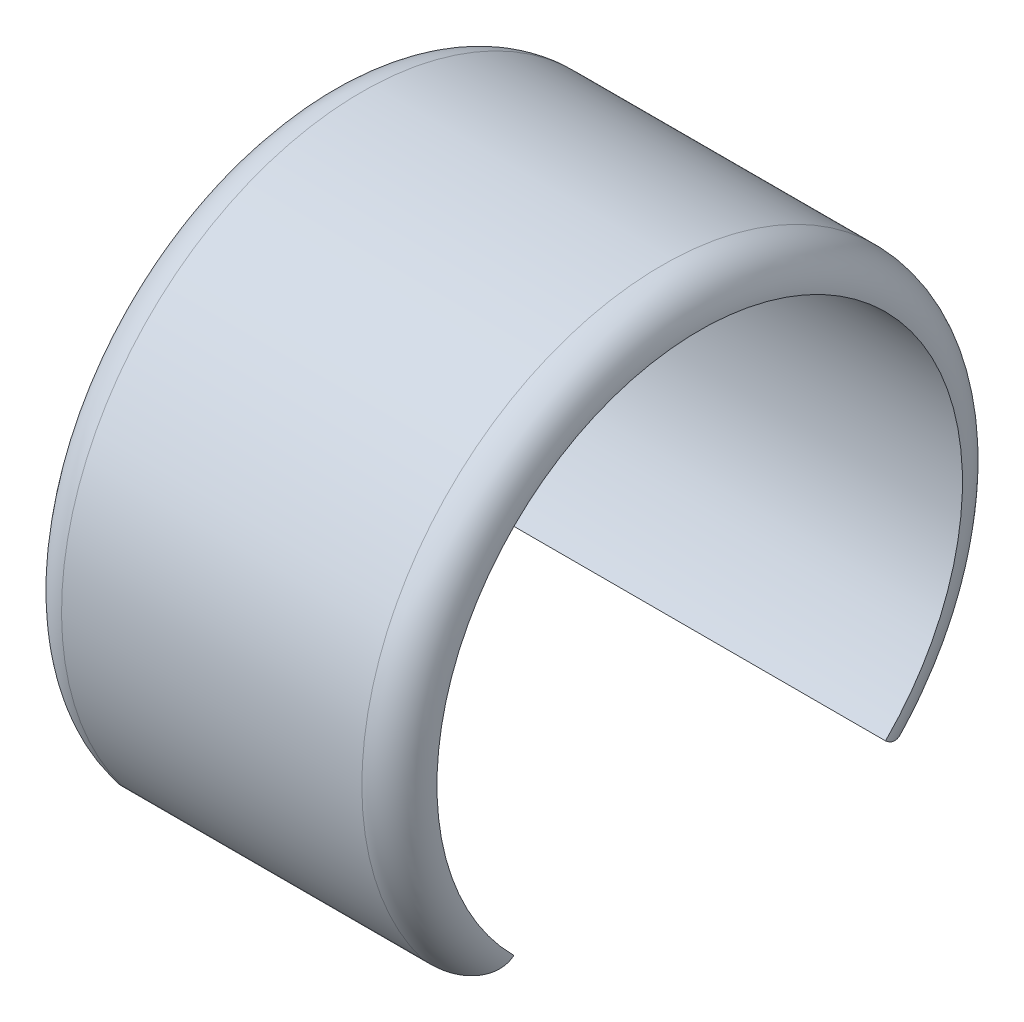
SolidWorks part; units mm, degrees
material "PUR"
ref_plane "Alzado" through (0, 0, 0) normal (0, 0, 1) x (1, 0, 0)
ref_plane "Planta" through (0, 0, 0) normal (0, 1, 0) x (1, 0, 0)
ref_plane "Vista lateral" through (0, 0, 0) normal (1, 0, 0) x (0, 0, -1)
sketch "Croquis1" plane through (0, 0, 0) normal (0, 0, 1) x (1, 0, 0)
  line L0 (-67.2609, 0) -> (67.2609, 0) construction
  line L1 (-50, 70) -> (50, 70)
  line L2 (-50, 70) -> (-50, 80)
  line L3 (-50, 80) -> (50, 80)
  line L4 (50, 70) -> (50, 80)
  point P4 (0, 80)
  point P9 (0, 0)
  dimension "D1" = 10
  dimension "D2" = 100
  dimension "D3" = 70
revolve "Revolución1" add sketch "Croquis1" angle 270 mid plane about L0
fillet "Redondeo1" radius 10 4 edges at (-50, 80, 0) (0, -56.5685, -56.5685) (50, 80, 0) (0, -56.5685, 56.5685)
equation "\"D3@Croquis1\"=80-\"D1@Croquis1\""
